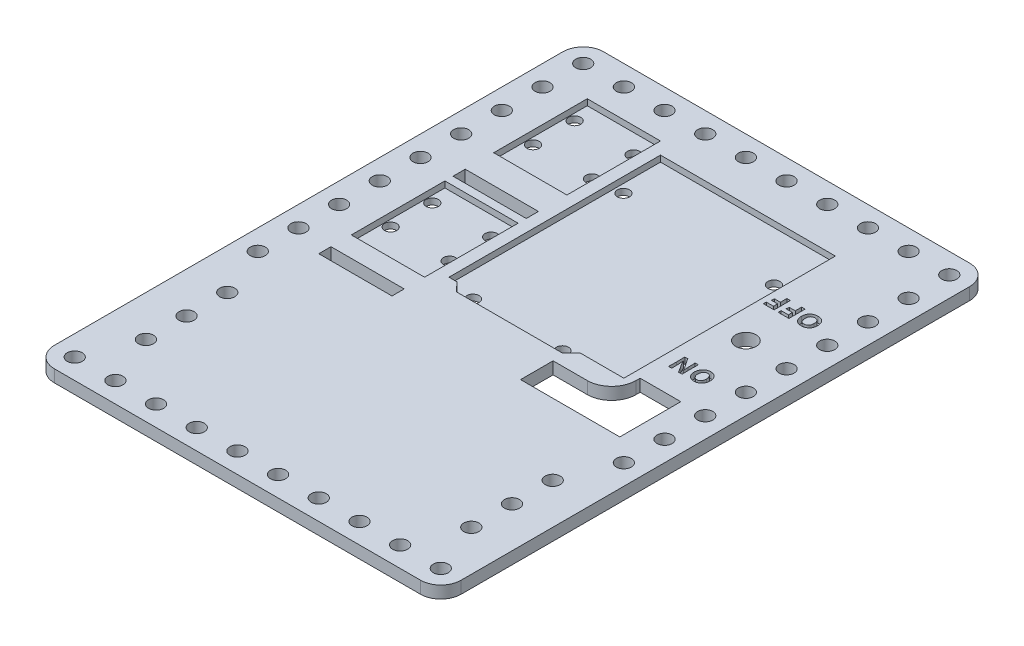
SolidWorks part; units mm, degrees
material "Copper"
ref_plane "Front Plane" through (0, 0, 0) normal (0, 0, 1) x (1, 0, 0)
ref_plane "Top Plane" through (0, 0, 0) normal (0, 1, 0) x (1, 0, 0)
ref_plane "Right Plane" through (0, 0, 0) normal (1, 0, 0) x (0, 0, -1)
sketch "Sketch1" plane through (0, 0, 0) normal (0, 1, 0) x (1, 0, 0)
  line L1 (6.35, 0) -> (120.65, 0)
  line L2 (0, 6.35) -> (0, 165.1)
  line L3 (6.35, 171.45) -> (120.65, 171.45)
  line L4 (127, 6.35) -> (127, 165.1)
  arc A0 (6.35, 0) -> (0, 6.35) centre (6.35, 6.35) cw
  arc A1 (120.65, 0) -> (127, 6.35) centre (120.65, 6.35) ccw
  arc A2 (120.65, 171.45) -> (127, 165.1) centre (120.65, 165.1) cw
  arc A3 (0, 165.1) -> (6.35, 171.45) centre (6.35, 165.1) cw
  point P7 (0, 0)
  point P10 (127, 0)
  point P13 (127, 171.45)
  point P16 (0, 171.45)
  dimension "D3" = 6.35
  dimension "D1" = 127
  dimension "D2" = 171.45
extrude "Plate Extrude" add sketch "Sketch1" along normal blind 3.81
sketch "Sketch2" plane through (0, 3.81, 0) normal (0, 1, 0) x (1, 0, 0)
  line L0 (120.65, 171.45) -> (6.35, 171.45) construction
  line L1 (0, 165.1) -> (0, 6.35) construction
  line L2 (6.35, 0) -> (120.65, 0) construction
  line L3 (63.5, 171.45) -> (63.5, 0) construction
  circle A0 centre (6.35, 165.1) radius 2.3495
  circle A1 centre (19.05, 165.1) radius 2.3495
  circle A2 centre (31.75, 165.1) radius 2.3495
  circle A3 centre (44.45, 165.1) radius 2.3495
  circle A4 centre (57.15, 165.1) radius 2.3495
  circle A5 centre (69.85, 165.1) radius 2.3495
  circle A6 centre (82.55, 165.1) radius 2.3495
  circle A7 centre (95.25, 165.1) radius 2.3495
  circle A8 centre (107.95, 165.1) radius 2.3495
  circle A9 centre (120.65, 165.1) radius 2.3495
  circle A10 centre (6.35, 152.4) radius 2.3495
  circle A11 centre (120.65, 152.4) radius 2.3495
  circle A12 centre (6.35, 139.7) radius 2.3495
  circle A13 centre (120.65, 139.7) radius 2.3495
  circle A14 centre (6.35, 127) radius 2.3495
  circle A15 centre (120.65, 127) radius 2.3495
  circle A16 centre (6.35, 114.3) radius 2.3495
  circle A17 centre (120.65, 114.3) radius 2.3495
  circle A18 centre (6.35, 101.6) radius 2.3495
  circle A19 centre (120.65, 101.6) radius 2.3495
  circle A20 centre (6.35, 88.9) radius 2.3495
  circle A21 centre (120.65, 88.9) radius 2.3495
  circle A22 centre (6.35, 76.2) radius 2.3495
  circle A23 centre (120.65, 76.2) radius 2.3495
  circle A24 centre (6.35, 63.5) radius 2.3495
  circle A25 centre (120.65, 63.5) radius 2.3495
  circle A26 centre (6.35, 6.35) radius 2.3495
  circle A27 centre (19.05, 6.35) radius 2.3495
  circle A28 centre (31.75, 6.35) radius 2.3495
  circle A29 centre (44.45, 6.35) radius 2.3495
  circle A30 centre (57.15, 6.35) radius 2.3495
  circle A31 centre (69.85, 6.35) radius 2.3495
  circle A32 centre (82.55, 6.35) radius 2.3495
  circle A33 centre (95.25, 6.35) radius 2.3495
  circle A34 centre (107.95, 6.35) radius 2.3495
  circle A35 centre (120.65, 6.35) radius 2.3495
  circle A36 centre (12.7, 22.225) radius 2.3495
  circle A37 centre (12.7, 34.925) radius 2.3495
  circle A38 centre (12.7, 47.625) radius 2.3495
  circle A39 centre (114.3, 47.625) radius 2.3495
  circle A40 centre (114.3, 34.925) radius 2.3495
  circle A41 centre (114.3, 22.225) radius 2.3495
  dimension "D1" = 4.699
  dimension "D2" = 6.35
  dimension "D6" = 4.699
  dimension "D7" = 6.35
  dimension "D8" = 6.35
  dimension "D10" = 4.699
  dimension "D11" = 12.7
  dimension "D12" = 22.225
  dimension "D3" = 6.35
  dimension "D4" = 10
  dimension "D5" = 9
  dimension "D9" = 10
  dimension "D13" = 3
extrude "Outer Hole Cut" cut sketch "Sketch2" against normal through all
sketch "Sketch3" plane through (0, 3.81, 0) normal (0, 1, 0) x (1, 0, 0)
  line L0 (81.28, 83.566) -> (84.074, 86.36)
  line L1 (43.18, 152.4) -> (97.79, 152.4)
  line L2 (43.18, 152.4) -> (43.18, 86.36)
  line L3 (43.18, 86.36) -> (97.79, 86.36)
  line L4 (97.79, 152.4) -> (97.79, 86.36)
  line L5 (81.28, 83.566) -> (48.26, 83.566)
  line L6 (48.26, 83.566) -> (45.72, 86.36)
  line L7 (127, 6.35) -> (127, 165.1) construction
  line L8 (120.65, 171.45) -> (6.35, 171.45) construction
  circle A0 centre (78.867, 86.106) radius 1.905
  circle A1 centre (50.927, 86.106) radius 1.905
  circle A2 centre (94.107, 136.906) radius 1.905
  circle A3 centre (45.847, 138.176) radius 1.905
  dimension "D1" = 3.81
  dimension "D9" = 52.07
  dimension "D2" = 54.61
  dimension "D3" = 66.04
  dimension "D4" = 40.894
  dimension "D5" = 38.1
  dimension "D6" = 5.08
  dimension "D7" = 27.94
  dimension "D8" = 7.747
  dimension "D10" = 50.8
  dimension "D11" = 15.24
  dimension "D12" = 5.08
  dimension "D13" = 2.54
  dimension "D14" = 2.794
  dimension "D15" = 2.54
  dimension "D16" = 29.21
  dimension "D17" = 19.05
extrude "Arduino Shape Cut" cut sketch "Sketch3" against normal blind 1.905 contours A1 L3 A0 L4 L1 L2 A3 A2 | A1 L3 L6 L5 L0 A0 region at (64.8255, 3.81, -84.9307) region at (70.503, 3.81, -119.3498)
sketch "Sketch4" plane through (0, 3.81, 0) normal (0, 1, 0) x (1, 0, 0)
  line L0 (43.18, 152.4) -> (43.18, 86.36) construction
  line L1 (16.51, 127) -> (39.37, 127)
  line L2 (16.51, 127) -> (16.51, 156.21)
  line L3 (16.51, 156.21) -> (39.37, 156.21)
  line L4 (39.37, 127) -> (39.37, 156.21)
  line L5 (43.18, 152.4) -> (97.79, 152.4) construction
  line L6 (16.51, 82.55) -> (39.37, 82.55)
  line L7 (16.51, 82.55) -> (16.51, 111.76)
  line L8 (39.37, 82.55) -> (39.37, 111.76)
  line L9 (16.51, 111.76) -> (39.37, 111.76)
  circle A0 centre (18.6057, 137.1834) radius 1.905
  circle A1 centre (18.6057, 150.1829) radius 1.905
  circle A2 centre (37.005, 150.1829) radius 1.905
  circle A3 centre (37.005, 137.1834) radius 1.905
  circle A4 centre (18.6057, 92.7334) radius 1.905
  circle A5 centre (18.6057, 105.7329) radius 1.905
  circle A6 centre (37.005, 105.7329) radius 1.905
  circle A7 centre (37.005, 92.7334) radius 1.905
  dimension "D1" = 3.81
  dimension "D9" = 18.3993
  dimension "D2" = 22.86
  dimension "D3" = 29.21
  dimension "D4" = 10.1834
  dimension "D5" = 2.365
  dimension "D6" = 3.81
  dimension "D7" = 12.9995
  dimension "D8" = 3.81
  dimension "D10" = 2
extrude "HG7881 Shape Cut" cut sketch "Sketch4" against normal blind 1.905 contours L1 L4 L3 L2 A3 A2 A1 A0 | L9 L7 L6 L8 A7 A6 A5 A4 region at (27.9499, 3.81, -141.4527) region at (27.9499, 3.81, -97.0027)
sketch "Sketch5" plane through (0, 3.81, 0) normal (0, 1, 0) x (1, 0, 0)
  circle A0 centre (94.107, 136.906) radius 1.905 construction
  circle A1 centre (78.867, 86.106) radius 1.905 construction
  circle A2 centre (50.927, 86.106) radius 1.905 construction
  circle A3 centre (45.847, 138.176) radius 1.905 construction
  circle A4 centre (18.6057, 150.1829) radius 1.905 construction
  circle A5 centre (37.005, 150.1829) radius 1.905 construction
  circle A6 centre (37.005, 137.1834) radius 1.905 construction
  circle A7 centre (18.6057, 137.1834) radius 1.905 construction
  circle A8 centre (18.6057, 105.7329) radius 1.905 construction
  circle A9 centre (18.6057, 92.7334) radius 1.905 construction
  circle A10 centre (37.005, 92.7334) radius 1.905 construction
  circle A11 centre (37.005, 105.7329) radius 1.905 construction
  circle A12 centre (94.107, 136.906) radius 1.905
  circle A13 centre (78.867, 86.106) radius 1.905
  circle A14 centre (50.927, 86.106) radius 1.905
  circle A15 centre (45.847, 138.176) radius 1.905
  circle A16 centre (18.6057, 150.1829) radius 1.905
  circle A17 centre (37.005, 150.1829) radius 1.905
  circle A18 centre (37.005, 137.1834) radius 1.905
  circle A19 centre (18.6057, 137.1834) radius 1.905
  circle A20 centre (18.6057, 105.7329) radius 1.905
  circle A21 centre (18.6057, 92.7334) radius 1.905
  circle A22 centre (37.005, 92.7334) radius 1.905
  circle A23 centre (37.005, 105.7329) radius 1.905
extrude "Arduino and HG7881 Hole Cut" cut sketch "Sketch5" against normal through all
sketch "Sketch6" plane through (0, 3.81, 0) normal (0, 1, 0) x (1, 0, 0)
  line L0 (97.79, 133.35) -> (115.57, 133.35) construction
  line L1 (97.79, 152.4) -> (97.79, 86.36) construction
  line L2 (120.65, 171.45) -> (6.35, 171.45) construction
  line L3 (106.68, 101.6) -> (106.68, 133.35) construction
  line L4 (97.79, 101.6) -> (115.57, 101.6) construction
  circle A0 centre (106.68, 115.57) radius 3.175
  text T0 "OFF" font "Dubai" height 5.08
  text T1 "ON" font "Candara" height 5.08
  point P6 (0, 0)
  point P10 (0, 0)
  dimension "D4" = 6.35
  dimension "D1" = 17.78
  dimension "D2" = 31.75
  dimension "D3" = 38.1
  dimension "D5" = 13.97
extrude "On-Off Text Cut" cut sketch "Sketch6" against normal blind 1.905
sketch "Sketch8" plane through (0, 1.905, 0) normal (0, 1, 0) x (1, 0, 0)
  circle A0 centre (106.68, 115.57) radius 3.175 construction
  circle A1 centre (106.68, 115.57) radius 3.175
extrude "Switch Hole Cut" cut sketch "Sketch8" against normal through all
sketch "Sketch9" plane through (0, 3.81, 0) normal (0, 1, 0) x (1, 0, 0)
  line L0 (113.03, 69.85) -> (82.0443, 69.85)
  line L1 (82.0443, 69.85) -> (82.0443, 80.01)
  line L2 (113.03, 69.85) -> (113.03, 88.9)
  line L3 (113.03, 88.9) -> (100.33, 88.9)
  line L4 (100.33, 88.9) -> (100.33, 87.63)
  line L5 (92.71, 80.01) -> (82.0443, 80.01)
  line L6 (97.79, 152.4) -> (97.79, 86.36) construction
  line L7 (84.074, 86.36) -> (97.79, 86.36) construction
  arc A0 (100.33, 87.63) -> (92.71, 80.01) centre (92.71, 87.63) cw
  dimension "D7" = 7.62
  dimension "D1" = 12.7
  dimension "D2" = 2.54
  dimension "D3" = 19.05
  dimension "D4" = 10.16
  dimension "D5" = 30.9857
  dimension "D6" = 2.54
extrude "Battery Wire Cut" cut sketch "Sketch9" against normal through all
sketch "Sketch10" plane through (0, 3.81, 0) normal (0, 1, 0) x (1, 0, 0)
  line L0 (16.51, 82.55) -> (16.51, 111.76) construction
  line L1 (39.37, 114.3) -> (16.51, 114.3)
  line L2 (39.37, 114.3) -> (39.37, 118.11)
  line L3 (39.37, 118.11) -> (16.51, 118.11)
  line L4 (16.51, 114.3) -> (16.51, 118.11)
  line L5 (39.37, 82.55) -> (39.37, 111.76) construction
  line L6 (16.51, 127) -> (39.37, 127) construction
  line L7 (39.37, 72.39) -> (16.51, 72.39)
  line L8 (39.37, 72.39) -> (39.37, 76.2)
  line L9 (39.37, 76.2) -> (16.51, 76.2)
  line L10 (16.51, 72.39) -> (16.51, 76.2)
  line L11 (16.51, 82.55) -> (39.37, 82.55) construction
  dimension "D1" = 3.81
  dimension "D2" = 12.7
  dimension "D3" = 3.81
  dimension "D4" = 10.16
extrude "Motor Wire Cut" cut sketch "Sketch10" against normal through all
